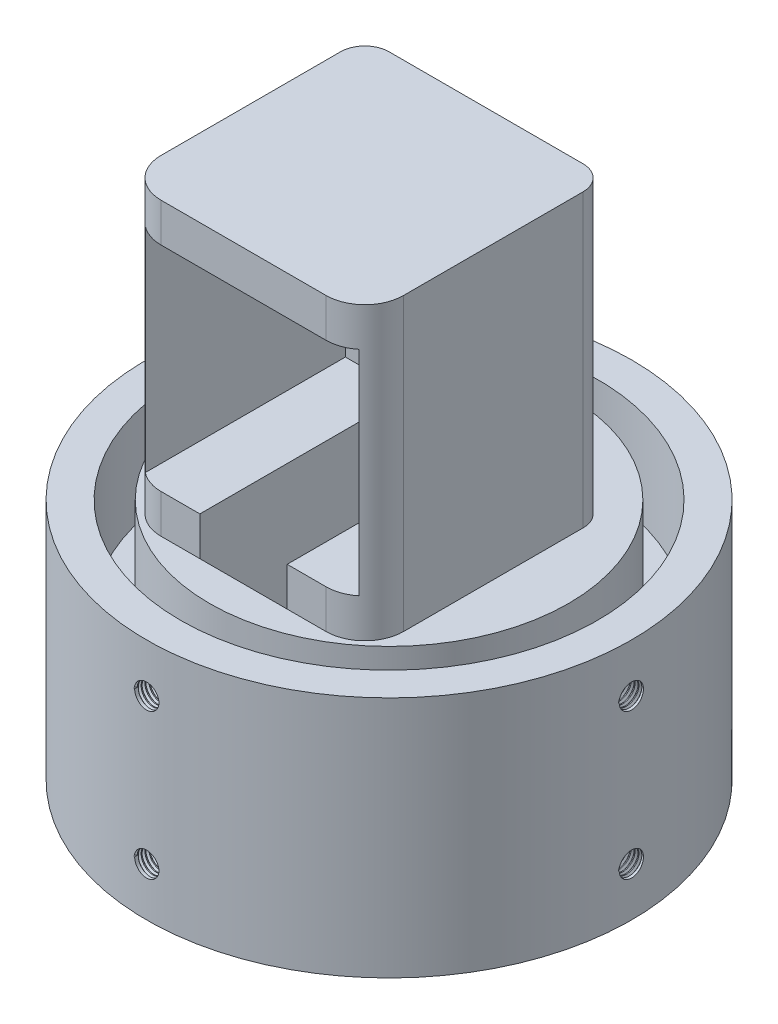
SolidWorks part; units mm, degrees
ref_plane "Front Plane" through (0, 0, 0) normal (0, 0, 1) x (1, 0, 0)
ref_plane "Top Plane" through (0, 0, 0) normal (0, 1, 0) x (1, 0, 0)
ref_plane "Right Plane" through (0, 0, 0) normal (1, 0, 0) x (0, 0, -1)
sketch "Sketch1" plane through (0, 0, 0) normal (0, 1, 0) x (1, 0, 0)
  line L5 (-25, 25) -> (25, 25)
  line L6 (-25, 25) -> (-25, -25)
  line L7 (-25, -25) -> (25, -25)
  line L8 (25, 25) -> (25, -25)
  line L9 (-25, 25) -> (25, -25) construction
  line L10 (-25, -25) -> (25, 25) construction
  point P0 (0, 0)
  dimension "D1" = 50
  dimension "D2" = 50
extrude "Boss-Extrude1" add sketch "Sketch1" along normal blind 60
sketch "Sketch4" plane through (0, 0, 25) normal (0, 0, 1) x (1, 0, 0)
  line L1 (-22, 52) -> (22, 52)
  line L2 (-22, 52) -> (-22, 8)
  line L3 (-22, 8) -> (22, 8)
  line L4 (22, 52) -> (22, 8)
  line L5 (-22, 52) -> (22, 8) construction
  line L6 (-22, 8) -> (22, 52) construction
  line L8 (25, 60) -> (25, 0) construction
  point P0 (0, 30)
  dimension "D1" = 44
  dimension "D2" = 25
  dimension "D3" = 30
sketch "Sketch2" plane through (0, 0, 0) normal (0, -1, 0) x (-1, 0, 0)
  line L1 (-25, 25) -> (25, 25) construction
  circle A0 centre (0, 5) radius 50
  dimension "D1" = 20
extrude "Cut-Extrude1" cut sketch "Sketch4" against normal blind 43
extrude "Boss-Extrude2- Base " add sketch "Sketch2" along normal blind 50
hole_wizard "CSK for M4 Flat Head Machine Screw2" [suppressed] positions "Sketch7" profile "Sketch6" countersink size "M4" standard "ANSI Metric"
sketch "Sketch7" plane through (0, 0, 0) normal (0, 1, 0) x (1, 0, 0)
  point P0 (0, 47.5)
  dimension "D1" = 47.5
sketch "Sketch6" plane through (0, 0, -47.5) normal (1, 0, 0) x (0, 0, 1)
  line L0 (0, 0) -> (0, 5)
  line L1 (0, 5) -> (2.25, 5)
  line L2 (2.25, 5) -> (2.25, 2.45)
  line L3 (2.25, 2.45) -> (4.7, 0)
  line L5 (4.7, 0) -> (0, 0)
  line L6 (-2.25, 2.45) -> (-4.7, 0) construction
  line L11 (0, -6.35) -> (0, 107.95) construction
  dimension "Thru Hole Dia." = 4.5
  dimension "Thru Hole Depth" = 5
  dimension "Near C'Sink Dia." = 9.4
  dimension "Near C'Sink Angle" = 90
pattern_circular "CirPattern1" [suppressed] count 4 over 360
sketch "Sketch3 - M3 Layout" plane through (0, 0, -25) normal (0, 0, 1) x (1, 0, 0)
  line L0 (-25, 60) -> (-25, 0) construction
  line L2 (22, 52) -> (-22, 52) construction
  line L3 (-15.5, 45.5) -> (15.5, 45.5) construction
  line L4 (-15.5, 45.5) -> (-15.5, 14.5) construction
  line L5 (-15.5, 14.5) -> (15.5, 14.5) construction
  line L6 (15.5, 45.5) -> (15.5, 14.5) construction
  line L7 (-15.5, 45.5) -> (15.5, 14.5) construction
  line L8 (-15.5, 14.5) -> (15.5, 45.5) construction
  circle A0 centre (-15.5, 45.5) radius 1.55
  circle A1 centre (15.5, 45.5) radius 1.55
  circle A2 centre (15.5, 14.5) radius 1.55
  circle A3 centre (-15.5, 14.5) radius 1.55
  circle A4 centre (0, 30) radius 11.5
  point P29 (0, 30)
  dimension "D2" = 3.1
  dimension "D3" = 23
  dimension "D1" = 31
  dimension "D4" = 22
  dimension "D5" = 25
extrude "Cut-Extrude3" cut sketch "Sketch3 - M3 Layout" against normal blind 1 and the other way blind 8 contours A4
hole_wizard "CBORE for M3 Hex Head Machine Screw1" positions "Sketch12" profile "Sketch11" counterbore size "M3" standard "ANSI Metric" end condition through all
sketch "Sketch12" plane through (0, 0, -25) normal (0, 0, -1) x (-1, 0, 0)
  point P0 (-15.5, 45.5)
  point P3 (15.5, 45.5)
  point P6 (15.5, 14.5)
  point P9 (-15.5, 14.5)
sketch "Sketch11" plane through (15.5, 45.5, -25) normal (1, 0, 0) x (0, 1, 0)
  line L0 (0, 0) -> (0, 70)
  line L1 (0, 70) -> (1.7, 70)
  line L3 (1.7, 70) -> (1.7, 2.3)
  line L4 (1.7, 2.3) -> (4.2, 2.3)
  line L5 (4.2, 2.3) -> (4.2, 0)
  line L7 (4.2, 0) -> (0, 0)
  line L11 (0, -6.35) -> (0, 107.95) construction
  dimension "Thru Hole Dia." = 3.4
  dimension "Thru Hole Depth" = 70
  dimension "C'Bore Dia." = 8.4
  dimension "C'Bore Depth" = 2.3
sketch "Sketch14 - M3 layout" [suppressed] plane through (0, 0, 30) normal (0, 0, 1) x (1, 0, 0)
  line L0 (-15.5, 107.42) -> (15.5, 107.42) construction
  line L1 (-15.5, 107.42) -> (-15.5, 76.42) construction
  line L2 (-15.5, 76.42) -> (15.5, 76.42) construction
  line L3 (15.5, 107.42) -> (15.5, 76.42) construction
  line L4 (-15.5, 107.42) -> (15.5, 76.42) construction
  line L5 (-15.5, 76.42) -> (15.5, 107.42) construction
  line L8 (-30, 69.92) -> (-30, 0) construction
  line L9 (22, 113.92) -> (-22, 113.92) construction
  circle A0 centre (-15.5, 107.42) radius 1.55
  circle A1 centre (15.5, 107.42) radius 1.55
  circle A2 centre (15.5, 76.42) radius 1.55
  circle A3 centre (-15.5, 76.42) radius 1.55
  circle A4 centre (0, 91.92) radius 11.5
  point P10 (0, 91.92)
  dimension "D1" = 3.1
  dimension "D2" = 23
  dimension "D3" = 22
  dimension "D4" = 30
sketch "Sketch19" plane through (25, 0, 0) normal (1, 0, 0) x (0, 0, -1)
  line L0 (-23, 91.92) -> (12, 91.92) construction
  line L2 (12, 91.92) -> (25, 91.92) construction
  line L9 (12, 113.92) -> (25, 113.92)
  line L10 (12, 113.92) -> (12, 69.92)
  line L11 (12, 69.92) -> (25, 69.92)
  line L12 (25, 113.92) -> (25, 69.92)
  line L13 (12, 113.92) -> (25, 69.92) construction
  line L14 (12, 69.92) -> (25, 113.92) construction
  point P4 (18.5, 91.92)
  dimension "D1" = 35
  dimension "D2" = 13
sketch "Sketch20" plane through (0, 8, 0) normal (0, 1, 0) x (1, 0, 0)
  line L0 (-9, 18) -> (-22, 18) construction
  line L2 (-9, 18) -> (9, 18) construction
  line L3 (9, 18) -> (22, 18) construction
  line L12 (-22, 18) -> (22, 18) construction
  line L14 (-22, -25) -> (22, -25) construction
  line L15 (-9, 18) -> (9, 18) construction
  line L16 (-9, 18) -> (-9, -25)
  line L17 (-9, -25) -> (9, -25)
  line L18 (9, 18) -> (9, -25)
  line L19 (-9, 18) -> (9, -25) construction
  line L20 (-9, -25) -> (9, 18) construction
  line L21 (-9, 18) -> (9, 18)
  point P5 (0, -3.5)
  point P10 (-0.5703, -3.5)
  dimension "D1" = 13
  dimension "D2" = 18
extrude "Cut-Extrude6- Wire Hole" cut sketch "Sketch20" against normal through all
fillet "Fillet1" radius 8 2 edges at (25, 30, 25) (-25, 30, 25)
sketch "Sketch26" plane through (0, 60, 0) normal (0, -1, 0) x (1, 0, 0)
  circle A2 centre (0, -5) radius 50
  circle A3 centre (0, -5) radius 50 construction
  dimension "D1" = 0
extrude "Boss-Extrude3 - Pipe" [suppressed] add sketch "Sketch26" against normal blind 40 contours A2
sketch "Sketch27" [suppressed] plane through (0, 100, 0) normal (0, 1, 0) x (1, 0, 0)
  circle A0 centre (0, 10) radius 41.275
  circle A1 centre (0, 10) radius 38.1
  circle A3 centre (0, 10) radius 50 construction
  dimension "D1" = 82.55
  dimension "D2" = 76.2
  dimension "D3" = 0
extrude "Cut-Extrude4- Pipe" [suppressed] cut sketch "Sketch27" against normal blind 30
ref_plane "Plane1" [suppressed] through (50, 0, 0) normal (1, 0, 0) x (0, 0, -1)
sketch "Sketch33" [suppressed] plane through (50, 0, 0) normal (1, 0, 0) x (0, 0, -1)
  line L0 (60, 109.92) -> (-40, 109.92) construction
  circle A0 centre (0, 102.92) radius 2.5
  dimension "D1" = 5
  dimension "D2" = 7
sketch "Sketch34" [suppressed] plane through (0, 109.92, 0) normal (0, 1, 0) x (1, 0, 0)
  line L0 (-25, 26.7137) -> (25, 26.7137)
  arc A4 (-25, 26.7137) -> (25, 26.7137) centre (0, 18.3526) cw
  point P12 (0, 44.7137)
  dimension "D1" = 50
  dimension "D2" = 18
extrude "Cut-Extrude6" [suppressed] cut sketch "Sketch34" against normal up to surface (40 mm away)
ref_plane "Plane2" through (0, 0, 0) normal (-1, 0, 0) x (0, 0, 1)
sketch "Sketch35" [suppressed] plane through (30, 0, 0) normal (1, 0, 0) x (0, 0, -1)
  line L5 (25, 0) -> (49.7571, 69.92)
  line L6 (-40, 69.92) -> (60, 69.92) construction
  line L7 (49.7571, 69.92) -> (25, 69.92)
  line L9 (25, 0) -> (20.2945, 0)
  line L10 (-17, 0) -> (25, 0) construction
sketch "Sketch37" [suppressed] plane through (50, 0, 0) normal (1, 0, 0) x (0, 0, -1)
  line L0 (48.1, 109.92) -> (-28.1, 109.92) construction
  circle A0 centre (9.9988, 94.92) radius 2.5
  dimension "D1" = 5
  dimension "D2" = 15
extrude "Cut-Extrude7" [suppressed] cut sketch "Sketch37" against normal blind 10
pattern_circular "CirPattern2" [suppressed] count 4 every 90
fillet "Fillet2" radius 5 2 edges at (-25, 30, -25) (25, 30, -25)
sketch "Sketch39- Pipe Alignment" plane through (0, 0, 0) normal (0, 1, 0) x (1, 0, 0)
  circle A0 centre (0, 5) radius 43
  circle A1 centre (0, 5) radius 37
  dimension "D1" = 86
  dimension "D2" = 74
extrude "Cut-Extrude8" cut sketch "Sketch39- Pipe Alignment" against normal blind 20
ref_plane "Plane3" through (0, -25, 0) normal (0, 1, 0) x (1, 0, 0)
mirror "Mirror1" about plane through (0, -25, 0) normal (0, 1, 0) of "Cut-Extrude8"
ref_plane "Plane4" through (0, 0, 45) normal (0, 0, 1) x (1, 0, 0)
sketch "Sketch40" plane through (0, 0, 45) normal (0, 0, 1) x (1, 0, 0)
  line L0 (0, -50) -> (0, 0) construction
  line L1 (-9, -50) -> (9, -50) construction
  circle A0 centre (0, -10) radius 2.5
  circle A1 centre (0, -40) radius 2.5
  dimension "D1" = 5
  dimension "D3" = 5
  dimension "D2" = 10
  dimension "D4" = 10
extrude "Cut-Extrude9" cut sketch "Sketch40" against normal blind 11
thread "Thread1" pitch 0.8 start angle 0, offset 0, length 10, pitch 0.8, diameter 5
ref_plane "Plane5" through (-2.5, -10, 45) normal (0, -1, 0) x (-1, 0, 0)
sketch "Thread Profile1" plane through (-2.5, -10, 45) normal (0, -1, 0) x (-1, 0, 0)
  line L0 (0, 0) -> (0, 0.8) construction
  line L1 (0, 0) -> (0.433, 0.25)
  line L2 (0.433, 0.25) -> (0.433, 0.35)
  line L3 (0.433, 0.35) -> (0, 0.6)
  line L4 (0.433, 0.3) -> (0, 0.3) construction
  line L11 (0, 0) -> (0, 0.6)
  point P2 (0, 0)
  dimension "Pitch" = 0.8
  dimension "Profile_Angle" = 60
  dimension "Profile_Land" = 0.1
  dimension "Profile_Height" = 0.433
thread "Thread2" pitch 0.8 profile "Thread Profile2" start angle 0, offset 0, length 10, pitch 0.8, diameter 5
ref_plane "Plane6" through (-2.5, -40, 45) normal (0, -1, 0) x (-1, 0, 0)
sketch "Thread Profile2" plane through (-2.5, -40, 45) normal (0, -1, 0) x (-1, 0, 0)
  line L0 (0, 0) -> (0, 0.8) construction
  line L1 (0, 0) -> (0.433, 0.25)
  line L2 (0.433, 0.25) -> (0.433, 0.35)
  line L3 (0.433, 0.35) -> (0, 0.6)
  line L4 (0.433, 0.3) -> (0, 0.3) construction
  line L11 (0, 0) -> (0, 0.6)
  point P2 (0, 0)
  dimension "Pitch" = 0.8
  dimension "Profile_Angle" = 60
  dimension "Profile_Land" = 0.1
  dimension "Profile_Height" = 0.433
pattern_circular "CirPattern6" count 4 over 360 about axis through (0, -50, -5) along (0, 1, 0) of "Cut-Extrude9"
ref_plane "Plane9" through (50, 0, 0) normal (1, 0, 0) x (0, 0, -1)
thread "Thread3" pitch 0.8 profile "Thread Profile3" start angle 0, offset 0, length 0, pitch 0.8, diameter 5
ref_plane "Plane10" through (50, -10, -2.5) normal (0, -1, 0) x (0, 0, 1)
sketch "Thread Profile3" plane through (50, -10, -2.5) normal (0, -1, 0) x (0, 0, 1)
  line L0 (0, 0) -> (0, 0.8) construction
  line L1 (0, 0) -> (0.433, 0.25)
  line L2 (0.433, 0.25) -> (0.433, 0.35)
  line L3 (0.433, 0.35) -> (0, 0.6)
  line L4 (0.433, 0.3) -> (0, 0.3) construction
  line L11 (0, 0) -> (0, 0.6)
  point P2 (0, 0)
  dimension "Pitch" = 0.8
  dimension "Profile_Angle" = 60
  dimension "Profile_Land" = 0.1
  dimension "Profile_Height" = 0.433
thread "Thread4" pitch 0.8 profile "Thread Profile4" start angle 0, offset 0, length 0, pitch 0.8, diameter 5
ref_plane "Plane11" through (50, -40, -2.5) normal (0, -1, 0) x (0, 0, 1)
sketch "Thread Profile4" plane through (50, -40, -2.5) normal (0, -1, 0) x (0, 0, 1)
  line L0 (0, 0) -> (0, 0.8) construction
  line L1 (0, 0) -> (0.433, 0.25)
  line L2 (0.433, 0.25) -> (0.433, 0.35)
  line L3 (0.433, 0.35) -> (0, 0.6)
  line L4 (0.433, 0.3) -> (0, 0.3) construction
  line L11 (0, 0) -> (0, 0.6)
  point P2 (0, 0)
  dimension "Pitch" = 0.8
  dimension "Profile_Angle" = 60
  dimension "Profile_Land" = 0.1
  dimension "Profile_Height" = 0.433
thread "Thread6" pitch 0.8 profile "Thread Profile7" start angle 0, offset 100, length 0, pitch 0.8, diameter 5
ref_plane "Plane16" through (2.5, -10, -55) normal (0, -1, 0) x (1, 0, 0)
sketch "Thread Profile7" plane through (2.5, -10, -55) normal (0, -1, 0) x (1, 0, 0)
  line L0 (0, 0) -> (0, 0.8) construction
  line L1 (0, 0) -> (0.433, 0.25)
  line L2 (0.433, 0.25) -> (0.433, 0.35)
  line L3 (0.433, 0.35) -> (0, 0.6)
  line L4 (0.433, 0.3) -> (0, 0.3) construction
  line L11 (0, 0) -> (0, 0.6)
  point P2 (0, 0)
  dimension "Pitch" = 0.8
  dimension "Profile_Angle" = 60
  dimension "Profile_Land" = 0.1
  dimension "Profile_Height" = 0.433
thread "Thread7" pitch 0.8 profile "Thread Profile8" start angle 0, offset 100, length 0, pitch 0.8, diameter 5
ref_plane "Plane17" through (2.5, -40, -55) normal (0, -1, 0) x (1, 0, 0)
sketch "Thread Profile8" plane through (2.5, -40, -55) normal (0, -1, 0) x (1, 0, 0)
  line L0 (0, 0) -> (0, 0.8) construction
  line L1 (0, 0) -> (0.433, 0.25)
  line L2 (0.433, 0.25) -> (0.433, 0.35)
  line L3 (0.433, 0.35) -> (0, 0.6)
  line L4 (0.433, 0.3) -> (0, 0.3) construction
  line L11 (0, 0) -> (0, 0.6)
  point P2 (0, 0)
  dimension "Pitch" = 0.8
  dimension "Profile_Angle" = 60
  dimension "Profile_Land" = 0.1
  dimension "Profile_Height" = 0.433
thread "Thread8" pitch 0.8 profile "Thread Profile9" start angle 0, offset 102, length 0, pitch 0.8, diameter 5
ref_plane "Plane18" through (-52, -10, -7.5) normal (0, -1, 0) x (0, 0, -1)
sketch "Thread Profile9" plane through (-52, -10, -7.5) normal (0, -1, 0) x (0, 0, -1)
  line L0 (0, 0) -> (0, 0.8) construction
  line L1 (0, 0) -> (0.433, 0.25)
  line L2 (0.433, 0.25) -> (0.433, 0.35)
  line L3 (0.433, 0.35) -> (0, 0.6)
  line L4 (0.433, 0.3) -> (0, 0.3) construction
  line L11 (0, 0) -> (0, 0.6)
  point P2 (0, 0)
  dimension "Pitch" = 0.8
  dimension "Profile_Angle" = 60
  dimension "Profile_Land" = 0.1
  dimension "Profile_Height" = 0.433
thread "Thread9" pitch 0.8 profile "Thread Profile10" start angle 0, offset 102, length 0, pitch 0.8, diameter 5
ref_plane "Plane19" through (-52, -40, -7.5) normal (0, -1, 0) x (0, 0, -1)
sketch "Thread Profile10" plane through (-52, -40, -7.5) normal (0, -1, 0) x (0, 0, -1)
  line L0 (0, 0) -> (0, 0.8) construction
  line L1 (0, 0) -> (0.433, 0.25)
  line L2 (0.433, 0.25) -> (0.433, 0.35)
  line L3 (0.433, 0.35) -> (0, 0.6)
  line L4 (0.433, 0.3) -> (0, 0.3) construction
  line L11 (0, 0) -> (0, 0.6)
  point P2 (0, 0)
  dimension "Pitch" = 0.8
  dimension "Profile_Angle" = 60
  dimension "Profile_Land" = 0.1
  dimension "Profile_Height" = 0.433
